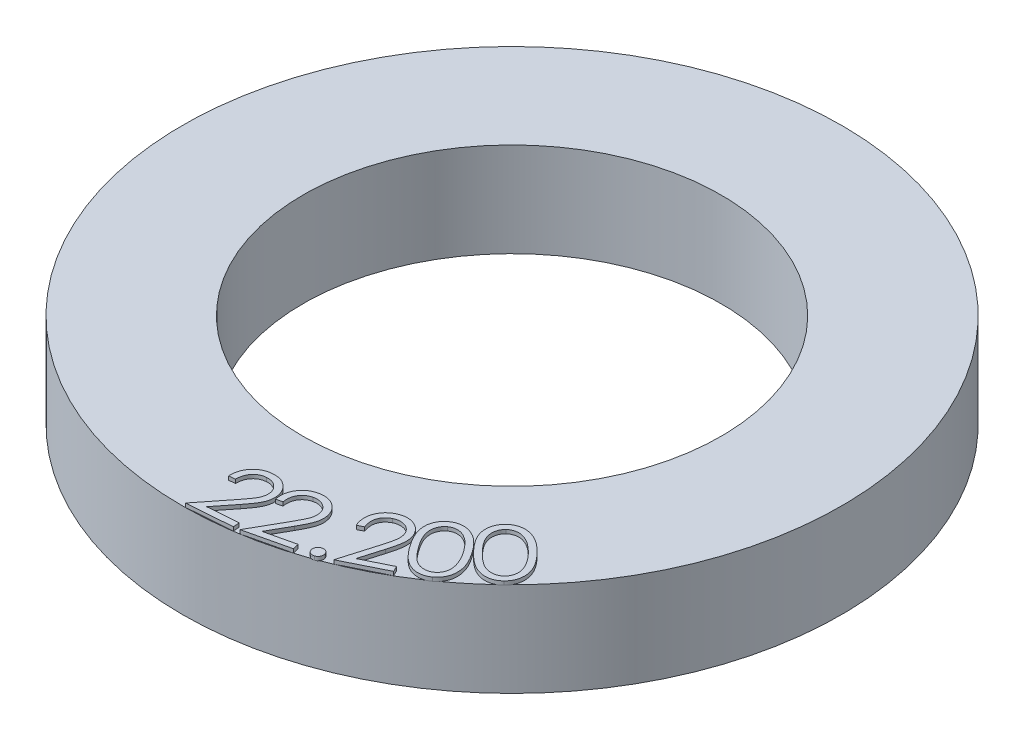
SolidWorks part; units mm, degrees
ref_plane "Front Plane" through (0, 0, 0) normal (0, 0, 1) x (1, 0, 0)
ref_plane "Top Plane" through (0, 0, 0) normal (0, 1, 0) x (1, 0, 0)
ref_plane "Right Plane" through (0, 0, 0) normal (1, 0, 0) x (0, 0, -1)
ref_axis "X" through (-88.99, 0, 0) along (1, 0, 0)
ref_axis "Y" through (0, 55, 0) along (0, -1, 0)
ref_axis "Z" through (0, 0, -88.99) along (0, 0, 1)
sketch "Sketch1" plane through (0, 0, 0) normal (0, 1, 0) x (1, 0, 0)
  circle A0 centre (0, 0) radius 17.5
  circle A1 centre (0, 0) radius 11.1
  dimension "D1" = 35
  dimension "D2" = 22.2
extrude "Boss-Extrude1" add sketch "Sketch1" along normal blind 5
sketch "Sketch9" plane through (0, 5, 0) normal (0, 1, 0) x (1, 0, 0)
  text T0 "22.200"
extrude "Boss-Extrude9" add sketch "Sketch9" along normal blind 0.2
